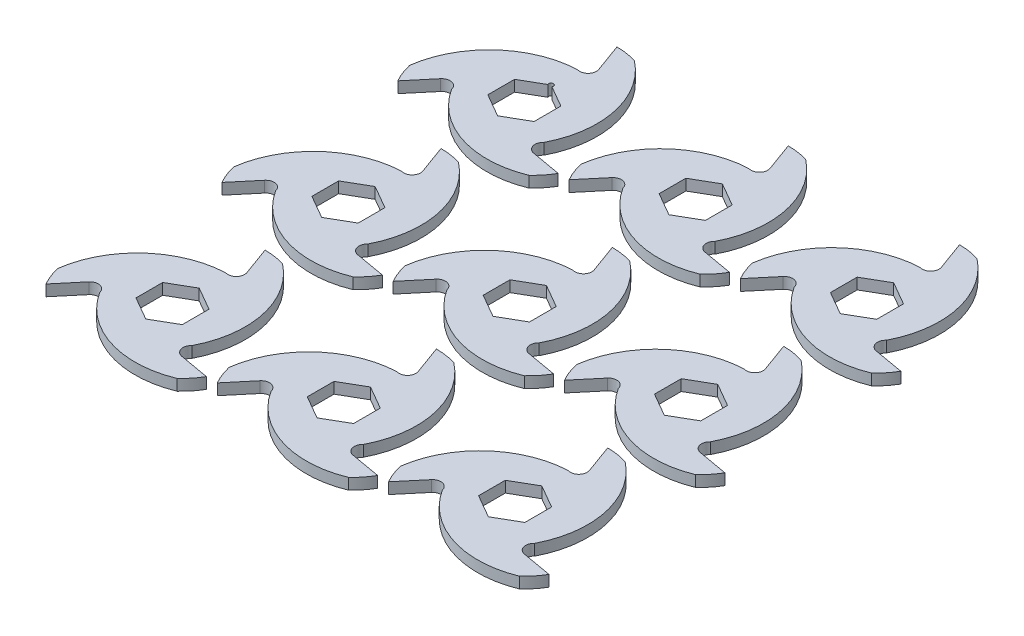
SolidWorks part; units mm, degrees
ref_plane "Front Plane" through (0, 0, 0) normal (0, 0, 1) x (1, 0, 0)
ref_plane "Top Plane" through (0, 0, 0) normal (0, 1, 0) x (1, 0, 0)
ref_plane "Right Plane" through (0, 0, 0) normal (1, 0, 0) x (0, 0, -1)
sketch "Sketch2" plane through (0, 0, 0) normal (0, 1, 0) x (1, 0, 0)
  line L0 (0, 50.8) -> (0, 0) construction
  line L1 (0, 0) -> (-43.9941, -25.4) construction
  line L2 (0, 0) -> (43.9941, -25.4) construction
  line L3 (0, 50.8) -> (5.6992, 35.1416)
  line L4 (43.9941, -25.4) -> (27.5839, -22.5064)
  line L5 (-43.9941, -25.4) -> (-33.2831, -12.6352)
  line L7 (0, 14.6647) -> (-12.7, 7.3323)
  line L8 (-12.7, 7.3323) -> (-12.7, -7.3323)
  line L9 (-12.7, -7.3323) -> (0, -14.6647)
  line L10 (0, -14.6647) -> (12.7, -7.3323)
  line L11 (12.7, -7.3323) -> (12.7, 7.3323)
  line L12 (12.7, 7.3323) -> (0, 14.6647)
  circle A0 centre (0, 0) radius 50.8 construction
  circle A1 centre (0, 13.2055) radius 37.5945
  circle A2 centre (11.4363, -6.6028) radius 37.5945
  circle A3 centre (-11.4363, -6.6028) radius 37.5945
  arc A4 (5.6992, 35.1416) -> (0, 29.21) centre (1.3938, 33.5746) cw
  arc A5 (27.5839, -22.5064) -> (25.2966, -14.605) centre (28.3796, -17.9943) cw
  arc A6 (-33.2831, -12.6352) -> (-25.2966, -14.605) centre (-29.7733, -15.5803) cw
  circle A7 centre (0, 0) radius 12.7 construction
  point P25 (0, 0)
  dimension "D1" = 101.6
  dimension "D4" = 20
  dimension "D2" = 120
  dimension "D3" = 120
  dimension "D5" = 21.59
  dimension "D8" = 25.4
  dimension "D7" = 3
extrude "Boss-Extrude2" add sketch "Sketch2" along normal mid plane 6.096 contours A1 A3 A2 L12 L11 L10 L9 L8 L7 | A1 A6 A2 A3 | L5 A6 A1 A3 | L4 A5 A3 A2 | A3 A5 A1 A2 | A2 A4 A3 A1 | L3 A4 A2 A1 region at (16.8055, 0, -37.817) region at (25.4344, 0, -14.5711) region at (-25.3361, 0, -14.7413) region at (-41.1532, 0, 4.3545) region at (18.3174, 0, -15.1298) region at (-0.0983, 0, 29.3123) region at (24.3477, 0, 33.4624)
sketch "Sketch3" plane through (0, 3.048, 0) normal (0, 1, 0) x (1, 0, 0)
  line L3 (43.9941, -25.4) -> (27.5839, -22.5064)
  line L4 (0, 50.8) -> (5.6992, 35.1416)
  line L5 (-43.9941, -25.4) -> (-33.2831, -12.6352)
  line L6 (43.9941, -25.4) -> (27.5839, -22.5064)
  line L7 (0, 50.8) -> (5.6992, 35.1416)
  line L8 (-43.9941, -25.4) -> (-33.2831, -12.6352)
  arc A0 (-48.1379, -14.7476) -> (0, 29.21) centre (2.2057, -21.5421) cw
  arc A1 (0, 29.21) -> (-43.9941, -25.4) centre (-11.4363, -6.6028) ccw construction
  arc A2 (0, 29.21) -> (5.6992, 35.1416) centre (1.3938, 33.5746) ccw construction
  arc A3 (11.2972, 49.0624) -> (25.2966, -14.605) centre (-19.7588, 8.8609) cw
  arc A4 (36.8407, -34.3148) -> (-25.2966, -14.605) centre (17.5532, 12.6812) cw
  arc A9 (-25.2966, -14.605) -> (-33.2831, -12.6352) centre (-29.7733, -15.5803) ccw
  arc A10 (-25.2966, -14.605) -> (43.9941, -25.4) centre (11.4363, -6.6028) ccw
  arc A11 (25.2966, -14.605) -> (27.5839, -22.5064) centre (28.3796, -17.9943) ccw
  arc A12 (25.2966, -14.605) -> (0, 50.8) centre (0, 13.2055) ccw
  arc A13 (0, 29.21) -> (5.6992, 35.1416) centre (1.3938, 33.5746) ccw
  arc A14 (0, 29.21) -> (-43.9941, -25.4) centre (-11.4363, -6.6028) ccw
  arc A15 (-25.2966, -14.605) -> (-33.2831, -12.6352) centre (-29.7733, -15.5803) ccw
  arc A16 (-25.2966, -14.605) -> (43.9941, -25.4) centre (11.4363, -6.6028) ccw
  arc A17 (25.2966, -14.605) -> (27.5839, -22.5064) centre (28.3796, -17.9943) ccw
  arc A18 (25.2966, -14.605) -> (0, 50.8) centre (0, 13.2055) ccw
  arc A19 (0, 29.21) -> (5.6992, 35.1416) centre (1.3938, 33.5746) ccw
  arc A20 (0, 29.21) -> (-43.9941, -25.4) centre (-11.4363, -6.6028) ccw
  point P26 (0, 0)
  arc M20 (-25.2966, -14.605) -> (43.9941, -25.4) centre (11.4363, -6.6028) ccw
  arc M23 (25.2966, -14.605) -> (0, 50.8) centre (0, 13.2055) ccw
  arc M26 (0, 29.21) -> (-43.9941, -25.4) centre (-11.4363, -6.6028) ccw
  dimension "D3" = 50.8
  dimension "D1" = 11.43
  dimension "D2" = 0
  dimension "D4" = 3
extrude "Cut-Extrude1" cut sketch "Sketch3" against normal through all contours A0 M26 | A3 M23 | A4 M20 region at (2.0677, 3.048, 36.1384) region at (30.2629, 3.048, -19.8599) region at (-32.3306, 3.048, -16.2785)
pattern_linear "LPattern1" count 3 spacing 96.52 along (0, 0, 1) count 3 spacing 93.98 along (1, 0, 0) of "Boss-Extrude2"
sketch "Sketch4" plane through (0, 3.048, 0) normal (0, 1, 0) x (1, 0, 0)
  circle A0 centre (0, 14.6647) radius 1.27
  dimension "D1" = 2.54
extrude "Cut-Extrude2" cut sketch "Sketch4" against normal through all
